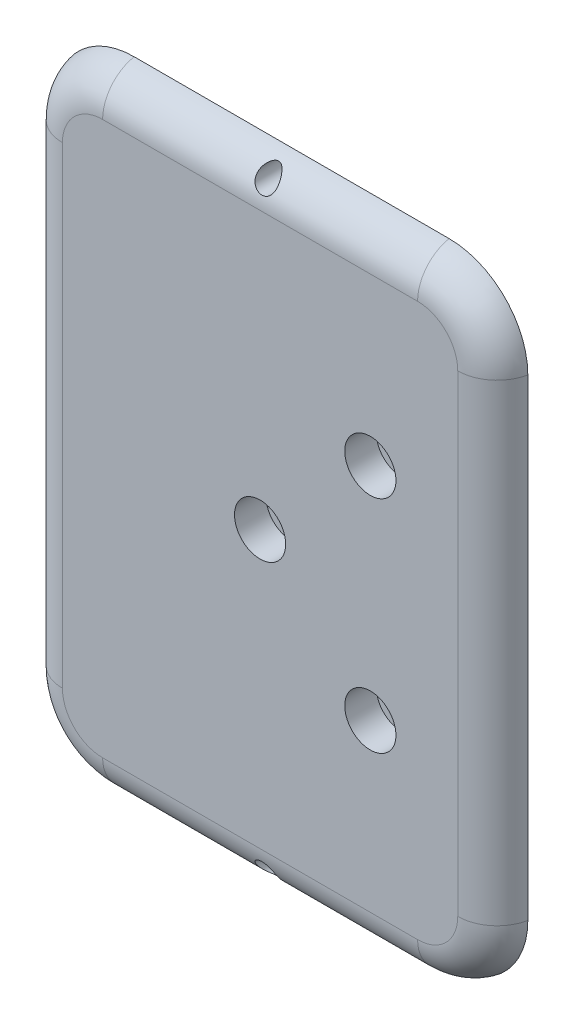
SolidWorks part; units mm, degrees
ref_plane "Front Plane" through (0, 0, 0) normal (0, 0, 1) x (1, 0, 0)
ref_plane "Top Plane" through (0, 0, 0) normal (0, 1, 0) x (1, 0, 0)
ref_plane "Right Plane" through (0, 0, 0) normal (1, 0, 0) x (0, 0, -1)
sketch "草圖1" plane through (0, 0, 0) normal (0, 0, 1) x (1, 0, 0)
  line L0 (25.7, -30) -> (25.7, 30)
  line L1 (20, 35.7) -> (-20, 35.7)
  line L2 (-25.7, 30) -> (-25.7, -30)
  line L3 (-20, -35.7) -> (20, -35.7)
  arc A0 (20, -35.7) -> (25.7, -30) centre (20, -30) ccw
  arc A1 (25.7, 30) -> (20, 35.7) centre (20, 30) ccw
  arc A2 (-20, 35.7) -> (-25.7, 30) centre (-20, 30) ccw
  arc A3 (-25.7, -30) -> (-20, -35.7) centre (-20, -30) ccw
extrude "填料-伸長1" add sketch "草圖1" along normal blind 3
sketch "草圖2" plane through (0, 0, 0) normal (0, 0, 1) x (1, 0, 0)
  line L0 (30, -30) -> (30, 30)
  line L1 (20, 40) -> (-20, 40)
  line L2 (-30, 30) -> (-30, -30)
  line L3 (-20, -40) -> (20, -40)
  arc A0 (20, -40) -> (30, -30) centre (20, -30) ccw
  arc A1 (30, 30) -> (20, 40) centre (20, 30) ccw
  arc A2 (-20, 40) -> (-30, 30) centre (-20, 30) ccw
  arc A3 (-30, -30) -> (-20, -40) centre (-20, -30) ccw
  circle A4 centre (0, 38) radius 1.35
  circle A5 centre (0, -38) radius 1.35
  circle A6 centre (0, 0) radius 3.25
  circle A7 centre (14, -14) radius 3.25
  circle A8 centre (14, 14) radius 3.25
extrude "填料-伸長2" add sketch "草圖2" along normal blind 4 from offset 3
fillet "圓角1" radius 5 8 edges at (27.0711, -37.0711, 7) (30, 0, 7) (27.0711, 37.0711, 7) (0, 40, 7) (-27.0711, 37.0711, 7) (-30, 0, 7) (-27.0711, -37.0711, 7) (0, -40, 7)
